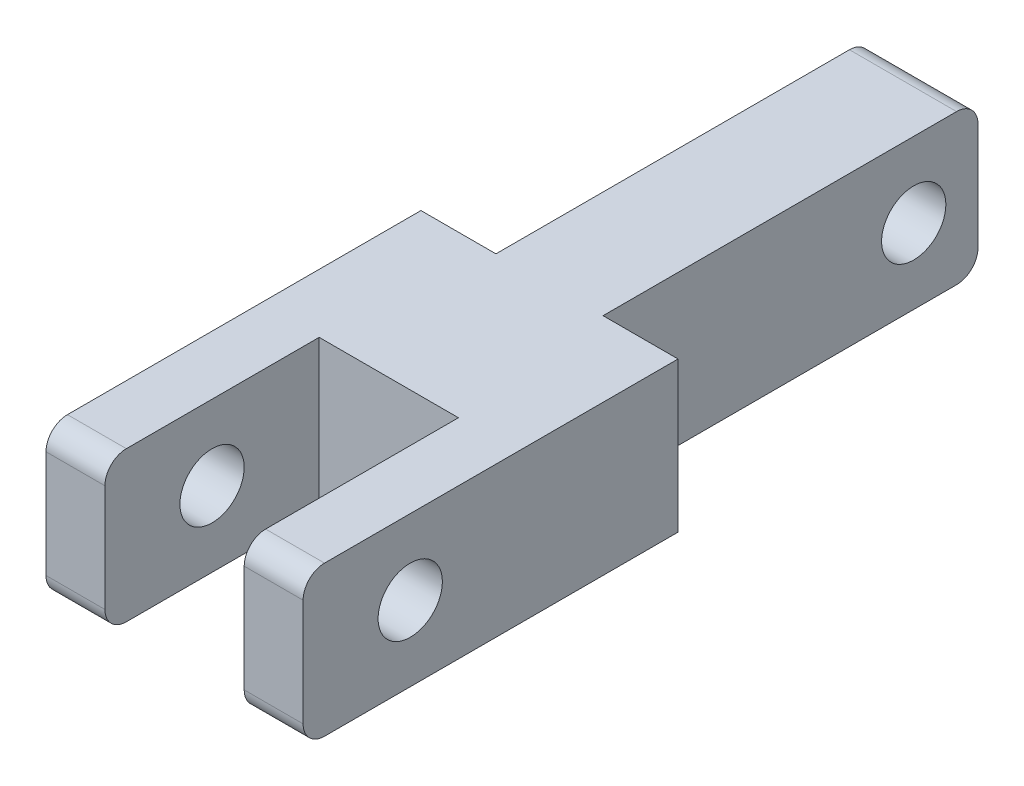
SolidWorks part; units mm, degrees
ref_plane "Alzado" through (0, 0, 0) normal (0, 0, 1) x (1, 0, 0)
ref_plane "Planta" through (0, 0, 0) normal (0, 1, 0) x (1, 0, 0)
ref_plane "Vista lateral" through (0, 0, 0) normal (1, 0, 0) x (0, 0, -1)
sketch "Croquis1" plane through (0, 0, 0) normal (1, 0, 0) x (0, 0, -1)
  line L0 (-16.5, 3.5) -> (16.5, 3.5)
  line L2 (-17.5, 0) -> (17.5, 0) construction
  line L3 (-17.5, 2.5) -> (-17.5, -2.5)
  line L4 (-16.5, -3.5) -> (16.5, -3.5)
  line L5 (17.5, 2.5) -> (17.5, -2.5)
  arc A0 (-17.5, -2.5) -> (-16.5, -3.5) centre (-16.5, -2.5) ccw
  arc A1 (-17.5, 2.5) -> (-16.5, 3.5) centre (-16.5, 2.5) cw
  arc A2 (16.5, -3.5) -> (17.5, -2.5) centre (16.5, -2.5) ccw
  arc A3 (16.5, 3.5) -> (17.5, 2.5) centre (16.5, 2.5) cw
  point P1 (0, 0)
  point P9 (-17.5, -3.5)
  point P13 (-17.5, 3.5)
  point P16 (17.5, -3.5)
  point P19 (17.5, 3.5)
  dimension "D3" = 1
  dimension "D4" = 1
  dimension "D1" = 3.5
  dimension "D2" = 35
extrude "Saliente-Extruir1" add sketch "Croquis1" along normal mid plane 5
sketch "Croquis2" plane through (0, 0, 0) normal (1, 0, 0) x (0, 0, -1)
  line L0 (-17.5, 2.5) -> (-17.5, -2.5) construction
  line L1 (17.5, -2.5) -> (17.5, 2.5) construction
  circle A0 centre (-12.5, 0) radius 1.5
  circle A1 centre (14.5, 0) radius 1.5
  dimension "D1" = 3
  dimension "D3" = 3
  dimension "D2" = 5
  dimension "D4" = 3
extrude "Cortar-Extruir1" cut sketch "Croquis2" against normal through all both and the other way through all
sketch "Croquis3" plane through (0, 0, 0) normal (1, 0, 0) x (0, 0, -1)
  line L0 (-17.5, 2.5) -> (-17.5, -2.5) construction
  line L1 (-17.5, 2.5) -> (-17.5, -2.5)
  line L2 (-16.5, 3.5) -> (0, 3.5)
  line L3 (16.5, 3.5) -> (-16.5, 3.5) construction
  line L4 (0, 3.5) -> (0, -3.5)
  line L5 (-16.5, -3.5) -> (16.5, -3.5) construction
  line L6 (0, -3.5) -> (-16.5, -3.5)
  circle A0 centre (-12.5, 0) radius 1.5 construction
  circle A1 centre (-12.5, 0) radius 1.5
  arc A2 (-16.5, 3.5) -> (-17.5, 2.5) centre (-16.5, 2.5) ccw construction
  arc A3 (-16.5, 3.5) -> (-17.5, 2.5) centre (-16.5, 2.5) ccw
  arc A4 (-17.5, -2.5) -> (-16.5, -3.5) centre (-16.5, -2.5) ccw construction
  arc A5 (-17.5, -2.5) -> (-16.5, -3.5) centre (-16.5, -2.5) ccw
extrude "Saliente-Extruir2" add sketch "Croquis3" along normal mid plane 12
sketch "Croquis4" plane through (0, 0, 0) normal (1, 0, 0) x (0, 0, -1)
  line L0 (-16.5, 3.5) -> (-7.5, 3.5)
  line L1 (0, 3.5) -> (-16.5, 3.5) construction
  line L2 (-7.5, 3.5) -> (-7.5, -3.5)
  line L3 (-16.5, -3.5) -> (0, -3.5) construction
  line L4 (-17.5, 2.5) -> (-17.5, -2.5)
  line L5 (-16.5, -3.5) -> (0, -3.5)
  line L6 (0, -3.5) -> (0, 3.5)
  line L7 (0, 3.5) -> (-16.5, 3.5)
  line L8 (-17.5, 2.5) -> (-17.5, -2.5)
  line L12 (-7.5, -3.5) -> (-16.5, -3.5)
  arc A2 (-16.5, 3.5) -> (-17.5, 2.5) centre (-16.5, 2.5) ccw
  arc A3 (-17.5, -2.5) -> (-16.5, -3.5) centre (-16.5, -2.5) ccw
  arc A4 (-16.5, 3.5) -> (-17.5, 2.5) centre (-16.5, 2.5) ccw
  arc A5 (-17.5, -2.5) -> (-16.5, -3.5) centre (-16.5, -2.5) ccw
  dimension "D2" = 10
  dimension "D1" = 0
extrude "Cortar-Extruir2" cut sketch "Croquis4" against normal mid plane 6.5
